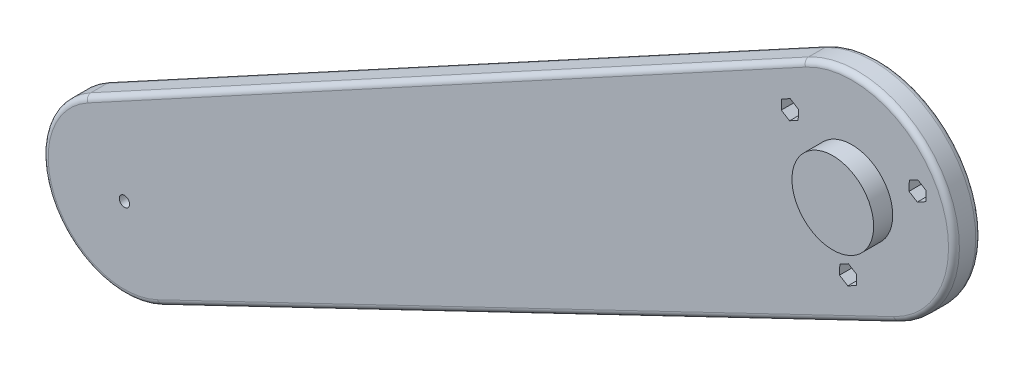
SolidWorks part; units mm, degrees
ref_plane "Front Plane" through (0, 0, 0) normal (0, 0, 1) x (1, 0, 0)
ref_plane "Top Plane" through (0, 0, 0) normal (0, 1, 0) x (1, 0, 0)
ref_plane "Right Plane" through (0, 0, 0) normal (1, 0, 0) x (0, 0, -1)
sketch "Sketch1" plane through (0, 0, 0) normal (0, 0, 1) x (1, 0, 0)
  line L3 (-281.4324, -110.2081) -> (-17.9006, 32.9518)
  line L4 (-254.127, -163.6138) -> (16.2311, -33.8053)
  arc A0 (16.2311, -33.8053) -> (-17.9006, 32.9518) centre (0, 0) ccw
  arc A1 (-281.4324, -110.2081) -> (-254.127, -163.6138) centre (-267.1119, -136.5695) ccw
  dimension "D1" = 75
  dimension "D2" = 60
  dimension "D3" = 300
extrude "Boss-Extrude1" add sketch "Sketch1" along normal blind 10
sketch "Sketch3" plane through (0, 0, 10) normal (0, 0, 1) x (1, 0, 0)
  line L2 (-4.4241, -25.1889) -> (-4.5358, -28.7672)
  line L3 (27.2927, 14.0337) -> (24.2497, 15.9196)
  line L4 (24.2497, 15.9196) -> (21.095, 14.2272)
  line L5 (21.095, 14.2272) -> (20.9833, 10.6489)
  line L6 (20.9833, 10.6489) -> (24.0263, 8.7631)
  line L7 (24.0263, 8.7631) -> (27.181, 10.4555)
  line L8 (27.181, 10.4555) -> (27.2927, 14.0337)
  line L9 (-4.5358, -28.7672) -> (-1.4928, -30.6531)
  line L10 (-1.4928, -30.6531) -> (1.6619, -28.9607)
  line L11 (1.6619, -28.9607) -> (1.7736, -25.3824)
  line L12 (1.7736, -25.3824) -> (-1.2694, -23.4965)
  line L13 (-1.2694, -23.4965) -> (-4.4241, -25.1889)
  line L14 (-19.6022, 16.4259) -> (-22.6452, 18.3117)
  line L15 (-22.6452, 18.3117) -> (-25.7999, 16.6193)
  line L16 (-25.7999, 16.6193) -> (-25.9116, 13.0411)
  line L17 (-25.9116, 13.0411) -> (-22.8686, 11.1552)
  line L18 (-22.8686, 11.1552) -> (-19.7139, 12.8476)
  line L19 (-19.7139, 12.8476) -> (-19.6022, 16.4259)
  circle A1 centre (24.138, 12.3413) radius 3.1004 construction
  point P28 (0, 0)
  dimension "D2" = 3.58
  dimension "D3" = 3
fillet "Fillet1" radius 2 8 edges at (33.389, 17.0712, 10) (-118.9479, -98.7095, 10) (-293.8231, -150.2264, 10) (-149.6665, -38.6281, 10) (-118.9479, -98.7095, 0) (33.389, 17.0712, 0) (-149.6665, -38.6281, 0) (-293.8231, -150.2264, 0)
ref_plane "Plane1" through (0, 0, 5) normal (0, 0, 1) x (1, 0, 0)
extrude "Cut-Extrude8" cut sketch "Sketch3" against normal blind 5
sketch "Sketch10" plane through (0, 0, 5) normal (0, 0, 1) x (1, 0, 0)
  circle A1 centre (24.0401, 12.2913) radius 1.75
  dimension "D1" = 3.5
extrude "Cut-Extrude9" cut sketch "Sketch10" against normal blind 70 and the other way blind 1 contours A1 | A1 region at (24.0401, 12.2913, 5)
pattern_circular "CirPattern1" count 3 over 360 about axis through (0, 0, 10) along (0, 0, -1) of "Cut-Extrude9" reverse direction yes
sketch "Sketch12" plane through (0, 0, 10) normal (0, 0, 1) x (1, 0, 0)
  circle A5 centre (0, 0) radius 15
  dimension "D1" = 30
extrude "Boss-Extrude2" add sketch "Sketch12" along normal blind 7
sketch "Sketch14" plane through (0, 0, 0) normal (0, 0, -1) x (-1, 0, 0)
  line L0 (0, 0) -> (267.1119, -136.5695)
  line L2 (270.6919, -136.5695) -> (268.9019, -133.4691)
  line L3 (268.9019, -133.4691) -> (265.3219, -133.4691)
  line L4 (265.3219, -133.4691) -> (263.5319, -136.5695)
  line L5 (263.5319, -136.5695) -> (265.3219, -139.6699)
  line L6 (265.3219, -139.6699) -> (268.9019, -139.6699)
  line L7 (268.9019, -139.6699) -> (270.6919, -136.5695)
  circle A0 centre (267.1119, -136.5695) radius 3.1004 construction
  dimension "D1" = 3.58
extrude "Cut-Extrude11" cut sketch "Sketch14" against normal blind 5 contours L6 L7 L2 L3 L4 L5 region at (-269.7149, -138.0723, 0)
sketch "Sketch15" plane through (0, 0, 5) normal (0, 0, -1) x (-1, 0, 0)
  circle A0 centre (267.1119, -136.5695) radius 1.9
  dimension "D1" = 3.8
extrude "Cut-Extrude12" cut sketch "Sketch15" against normal blind 5
